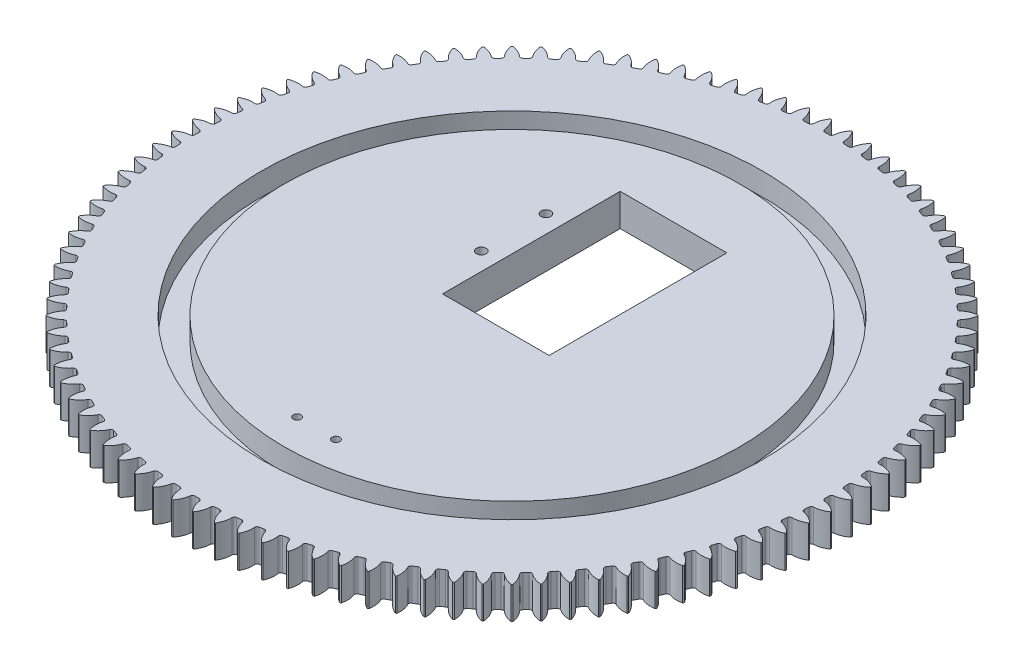
SolidWorks part; units mm, degrees
ref_plane "Front Plane" through (0, 0, 0) normal (0, 0, 1) x (1, 0, 0)
ref_plane "Top Plane" through (0, 0, 0) normal (0, 1, 0) x (1, 0, 0)
ref_plane "Right Plane" through (0, 0, 0) normal (1, 0, 0) x (0, 0, -1)
sketch "Sketch1" plane through (0, 0, 0) normal (0, 1, 0) x (1, 0, 0)
  circle A1 centre (0, 0) radius 102
  dimension "D2" = 204
extrude "Boss-Extrude1" add sketch "Sketch1" along normal blind 10
sketch "Sketch2" plane through (0, 10, 0) normal (0, 1, 0) x (1, 0, 0)
  line L0 (0, 0) -> (0, 102) construction
  line L1 (-1.3895, 97.4901) -> (0, 0) construction
  line L2 (0, 94.8463) -> (-2.5918, 101.9671) construction
  circle A0 centre (0, 0) radius 102 construction
  arc A1 (1.3895, 97.4901) -> (-1.3895, 97.4901) centre (0, 0) ccw
  arc A2 (1.8707, 99.9825) -> (-1.8707, 99.9825) centre (0, 0) ccw construction
  arc A3 (3.0148, 101.9554) -> (-3.0148, 101.9554) centre (0, 0) ccw
  arc A4 (-3.0148, 101.9554) -> (-1.3895, 97.4901) centre (-8.6195, 97.387) cw
  arc A5 (3.0148, 101.9554) -> (1.3895, 97.4901) centre (8.6195, 97.387) ccw
  point P16 (-1.8249, 99.8601)
  dimension "D1" = 204
  dimension "D2" = 200
  dimension "D3" = 4.5
  dimension "D4" = 20
  dimension "D5" = 3.7416
extrude "Cut-Extrude1" cut sketch "Sketch2" against normal through all
fillet "Fillet1" radius 0.76 2 edges at (1.3895, 5, -97.4901) (-1.3895, 5, -97.4901)
pattern_circular "CirPattern2" count 100 over 360 about axis through (0, 10, 0) along (0, 1, 0) of "Cut-Extrude1", "Fillet1"
sketch "Sketch3" plane through (0, 10, 0) normal (0, 1, 0) x (1, 0, 0)
  circle A0 centre (0, 0) radius 73 construction
  circle A1 centre (0, 0) radius 77.5
  circle A2 centre (0, 0) radius 70.5
  dimension "D1" = 146
  dimension "D2" = 7
  dimension "D3" = 4.5
extrude "Cut-Extrude2" cut sketch "Sketch3" against normal blind 7
sketch "Sketch4" plane through (0, 0, 0) normal (0, -1, 0) x (1, 0, 0)
  circle A0 centre (0, 0) radius 100 construction
  dimension "D1" = 200
sketch "Sketch6" plane through (0, 0, 0) normal (0, -1, 0) x (1, 0, 0)
  line L1 (-16.5, -50) -> (16.5, -50)
  line L2 (-16.5, -50) -> (-16.5, 5)
  line L3 (-16.5, 5) -> (16.5, 5)
  line L4 (16.5, -50) -> (16.5, 5)
  point P4 (0, 5)
  dimension "D1" = 33
  dimension "D2" = 55
  dimension "D3" = 5
extrude "Cut-Extrude3" cut sketch "Sketch6" against normal through all
ref_plane "Plane1" through (21.5, 0, 0) normal (1, 0, 0) x (0, 0, -1)
sketch "Sketch7" plane through (21.5, 0, 0) normal (1, 0, 0) x (0, 0, -1)
  line L1 (1.5, 0) -> (43.5, 0)
  line L2 (1.5, 0) -> (1.5, -47)
  line L3 (1.5, -47) -> (43.5, -47)
  line L4 (43.5, 0) -> (43.5, -47)
  line L5 (50, 10) -> (-5, 10) construction
  circle A0 centre (22.5, -26) radius 12
  circle A1 centre (7, -10.5) radius 1.65
  circle A2 centre (38, -10.5) radius 1.65
  circle A3 centre (38, -41.5) radius 1.65
  circle A4 centre (7, -41.5) radius 1.65
  point P5 (22.5, 0)
  point P18 (22.5, -47)
  point P21 (22.5, 10)
  dimension "D4" = 24
  dimension "D9" = 3.3
  dimension "D1" = 42
  dimension "D2" = 21
  dimension "D3" = 47
  dimension "D5" = 5.5
  dimension "D6" = 10.5
  dimension "D7" = 5.5
  dimension "D8" = 5.5
extrude "Boss-Extrude2" add sketch "Sketch7" along normal blind 5
sketch "Sketch9" plane through (0, 0, 0) normal (0, -1, 0) x (1, 0, 0)
  line L1 (26.5, -1.5) -> (68.5, -1.5)
  line L2 (26.5, -1.5) -> (26.5, -43.5)
  line L3 (26.5, -43.5) -> (68.5, -43.5)
  line L4 (68.5, -1.5) -> (68.5, -43.5)
  dimension "D1" = 42
extrude "Boss-Extrude3" add sketch "Sketch9" along normal blind 5
sketch "Sketch10" plane through (0, 0, 0) normal (0, -1, 0) x (1, 0, 0)
  line L0 (-6, 60.5) -> (6, 60.5) construction
  line L1 (68.5, -1.5) -> (21.5, -1.5) construction
  circle A0 centre (-6, 60.5) radius 1.2
  circle A1 centre (6, 60.5) radius 1.2
  point P2 (0, 60.5)
  dimension "D2" = 2.4
  dimension "D1" = 62
  dimension "D3" = 12
extrude "Cut-Extrude4" cut sketch "Sketch10" against normal through all
sketch "Sketch11" plane through (0, 0, 0) normal (0, -1, 0) x (1, 0, 0)
  line L0 (-16.5, 5) -> (-16.5, -50) construction
  line L1 (-16.5, -22.5) -> (16.5, -22.5) construction
  line L2 (16.5, -50) -> (16.5, 5) construction
  circle A0 centre (-22, -12.5) radius 1.5
  circle A1 centre (-22, -32.5) radius 1.5
  point P4 (-16.5, -22.5)
  dimension "D2" = 3
  dimension "D1" = 5.5
  dimension "D3" = 10
extrude "Cut-Extrude5" cut sketch "Sketch11" against normal through all
equation "\"Module\"= 2"
equation "\"No. of Teeth\"= 100"
equation "\"Bore Diameter\"=2"
equation "\"Pressure Angle\"= 20deg"
equation "\"Outer Diameter\"= ( \"No. of Teeth\" + 2 ) * \"Module\""
equation "\"Pitch Diameter\"= \"No. of Teeth\" * \"Module\""
equation "\"Backlash\"= 0.3 * \"Module\""
equation "\"Arc Length\"= ( \"Module\" * pi ) / 2 + \"Backlash\""
equation "\"Fillet Radius\"= .38 * \"Module\""
equation "\"Tooth Depth\"= IIF ( \"Module\" <= 1.25 , 2.4 * \"Module\" , 2.25 * \"Module\" )"
equation "\"D2@Sketch1\"=\"Outer Diameter\""
equation "\"D2@Sketch2\"=\"Pitch Diameter\""
equation "\"D1@Sketch2\"=\"Outer Diameter\""
equation "\"D3@Sketch2\"=\"Tooth Depth\""
equation "\"D4@Sketch2\"=\"Pressure Angle\""
equation "\"D5@Sketch2\"=\"Arc Length\""
equation "\"D1@Fillet1\"=\"Fillet Radius\""
equation "\"D1@CirPattern2\"=\"No. of Teeth\""
equation "\"D1@Sketch4\"=\"Pitch Diameter\""
